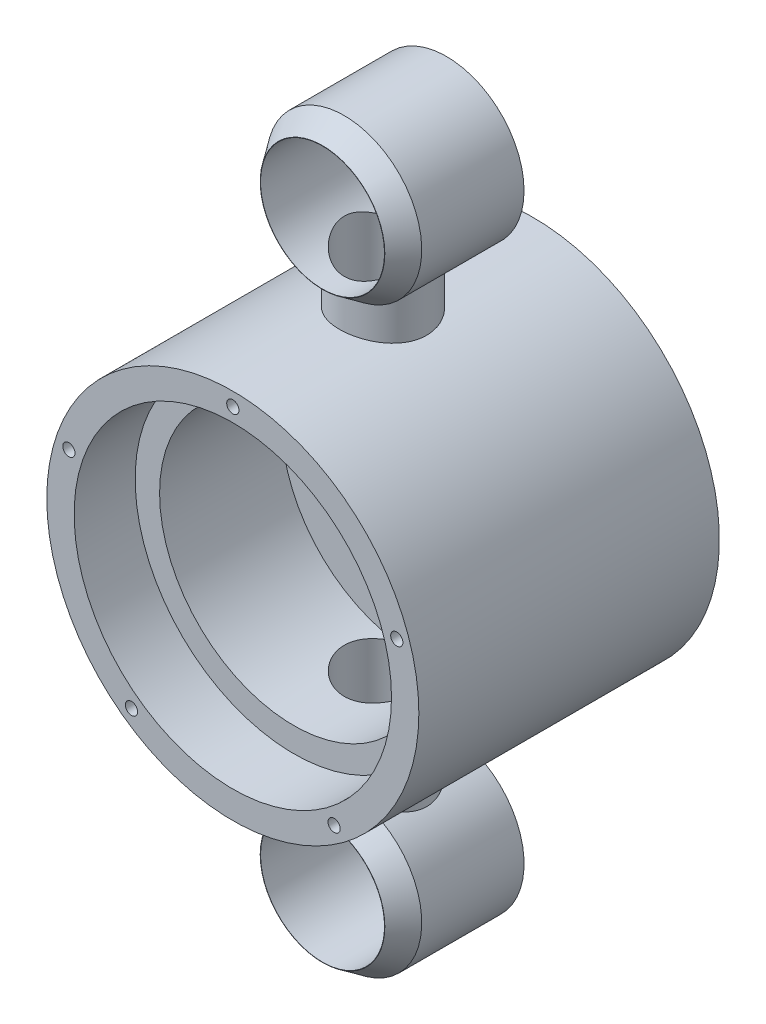
SolidWorks part; units mm, degrees
ref_plane "Front Plane" through (0, 0, 0) normal (1, 0, 0) x (0, 1, 0)
ref_plane "Top Plane" through (0, 0, 0) normal (0, 0, 1) x (0, 1, 0)
ref_plane "Right Plane" through (0, 0, 0) normal (0, 1, 0) x (-1, 0, 0)
sketch "Sketch2" plane through (0, 0, 0) normal (0, 0, 1) x (0, 1, 0)
  circle A0 centre (0, 0) radius 76.2
  dimension "D1" = 152.4
extrude "Boss-Extrude1" add sketch "Sketch2" along normal blind 85 contours A0
sketch "Sketch4" plane through (0, 0, 85) normal (0, 0, 1) x (1, 0, 0)
  circle A0 centre (0, 0) radius 65
  dimension "D1" = 130
extrude "Cut-Extrude2" cut sketch "Sketch4" against normal blind 25
sketch "Sketch5" plane through (0, 0, 60) normal (0, 0, 1) x (1, 0, 0)
  circle A0 centre (0, 0) radius 55
  dimension "D1" = 110
extrude "Cut-Extrude3" cut sketch "Sketch5" against normal blind 50
sketch "Sketch7" plane through (0, 0, 85) normal (0, 0, 1) x (1, 0, 0)
  circle A0 centre (0, 70.612) radius 2.5
  circle A1 centre (0, 0) radius 76.2 construction
  dimension "D1" = 5
  dimension "D2" = 70.612
extrude "Cut-Extrude4" cut sketch "Sketch7" against normal blind 20
pattern_circular "CirPattern1" count 5 over 360 about axis through (0, 0, 0) along (0, 0, 1) of "Cut-Extrude4"
sketch "Sketch8" plane through (0, 0, 0) normal (0, 0, -1) x (1, 0, 0)
  circle A0 centre (0, 0) radius 50.8
  circle A1 centre (0, 0) radius 76.2
  dimension "D1" = 101.6
  dimension "D2" = 152.4
extrude "Boss-Extrude2" add sketch "Sketch8" along normal blind 38.1
sketch "Sketch10" plane through (0, 0, 0) normal (0, 1, 0) x (-1, 0, 0)
  line L0 (-6.35, 0) -> (-6.35, -38.1)
  line L1 (-50.8, 0) -> (50.8, 0) construction
  line L2 (-50.8, -38.1) -> (50.8, -38.1) construction
  line L3 (-6.35, -38.1) -> (6.35, -38.1)
  line L4 (6.35, -38.1) -> (6.35, -6.35)
  line L5 (6.35, -6.35) -> (26.709, -6.35)
  line L6 (26.709, -6.35) -> (26.709, 0)
  line L7 (26.709, 0) -> (-6.35, 0)
  line L8 (0, -43.2967) -> (0, 13.2611) construction
  dimension "D1" = 6.35
  dimension "D2" = 6.35
  dimension "D3" = 6.35
extrude "Cut-Extrude5" cut sketch "Sketch10" against normal blind 66.04
sketch "Sketch19" plane through (0, 0, -6.35) normal (0, 0, 1) x (1, 0, 0)
  line L0 (-26.709, -58.6424) -> (-26.709, -66.04)
  line L1 (-26.709, -66.04) -> (-26.709, -43.2119) construction
  line L2 (-26.709, -66.04) -> (-6.35, -66.04)
  line L3 (-6.35, -66.04) -> (-6.35, -65.8321)
  spline S0 degree 2 poles (-26.709, -58.6424) (-17.6862, -65.3309) (-6.35, -65.8321) knots 0 0 0 1 1 1
  point P2 (0, 0)
  point P6 (0, 0)
  point P7 (0, 0)
  point P10 (0, 0)
extrude "Boss-Extrude5" add sketch "Sketch19" along normal blind 6.35
sketch "Sketch18" plane through (0, 0, -6.35) normal (0, 0, 1) x (1, 0, 0)
  line L0 (-26.709, -49.2572) -> (-26.709, -66.04)
  line L1 (-26.709, -58.6424) -> (-26.709, -43.2119) construction
  line L2 (-26.709, -66.04) -> (-6.35, -66.04)
  line L3 (-6.35, -65.8321) -> (-6.35, -50.4016) construction
  line L4 (-6.35, -66.04) -> (-6.35, -56.4469)
  spline S0 degree 2 poles (-26.709, -49.2572) (-17.3349, -55.1233) (-6.35, -56.4469) knots 0 0 0 1 1 1
  point P2 (0, 0)
  point P6 (-6.35, -62.912)
extrude "Cut-Extrude9" cut sketch "Sketch18" along normal blind 7.62
pattern_circular "CirPattern2" count 4 every 90 about axis through (0, 0, 0) along (0, 0, 1) of "Cut-Extrude5", "Boss-Extrude5"
sketch "Sketch12" plane through (0, 0, -38.1) normal (0, 0, -1) x (1, 0, 0)
  circle A2 centre (0, 0) radius 69.85
  dimension "D1" = 139.7
extrude "Cut-Extrude6" cut sketch "Sketch12" against normal blind 25.4
sketch "Sketch13" plane through (0, 0, 0) normal (0, 1, 0) x (-1, 0, 0)
  line L0 (0, 85) -> (0, -38.1) construction
  line L1 (2.5, 85) -> (-2.5, 85) construction
  line L2 (-76.2, -38.1) -> (76.2, -38.1) construction
  circle A0 centre (0, 23.45) radius 17.8367
extrude "Boss-Extrude3" add sketch "Sketch13" along normal blind 50.8 from offset 68.58
sketch "Sketch14" plane through (0, 0, 0) normal (0, 0, 1) x (0, 1, 0)
  line L0 (65, 0) -> (119.38, 0) construction
  line L1 (119.38, -17.8367) -> (119.38, 17.8367) construction
  circle A0 centre (0, 0) radius 65 construction
  circle A1 centre (0, 0) radius 65 construction
  circle A2 centre (119.38, 0) radius 31.75
  circle A3 centre (119.38, 0) radius 25.4
  dimension "D1" = 63.5
  dimension "D2" = 50.8
extrude "Boss-Extrude4" add sketch "Sketch14" along normal mid plane 50.8 from offset 22.86
sketch "Sketch17" plane through (0, 119.38, 0) normal (0, 1, 0) x (-1, 0, 0)
  line L0 (0, 41.2867) -> (0, 5.6133) construction
  circle A0 centre (0, 23.45) radius 17.8367 construction
  circle A1 centre (0, 23.45) radius 17.8367 construction
  circle A2 centre (0, 23.45) radius 15.875
  dimension "D1" = 31.75
extrude "Cut-Extrude8" cut sketch "Sketch17" against normal blind 73.66
sketch "Sketch16" plane through (0, 0, 48.26) normal (0, 0, 1) x (1, 0, 0)
  line L0 (17.8367, 119.38) -> (-17.8367, 119.38) construction
  circle A0 centre (0, 119.38) radius 25.4
extrude "Cut-Extrude7" cut sketch "Sketch16" against normal blind 50.8
chamfer "Chamfer1" distance 8.89 angle 35 1 edges at (31.75, 119.38, 48.26)
pattern_circular "CirPattern3" count 2 over 360 about axis through (0, 0, 0) along (0, 0, 1) of "Boss-Extrude3", "Cut-Extrude8", "Boss-Extrude4", "Cut-Extrude7", "Chamfer1"
equation "\"o.2\"=0.187569"
